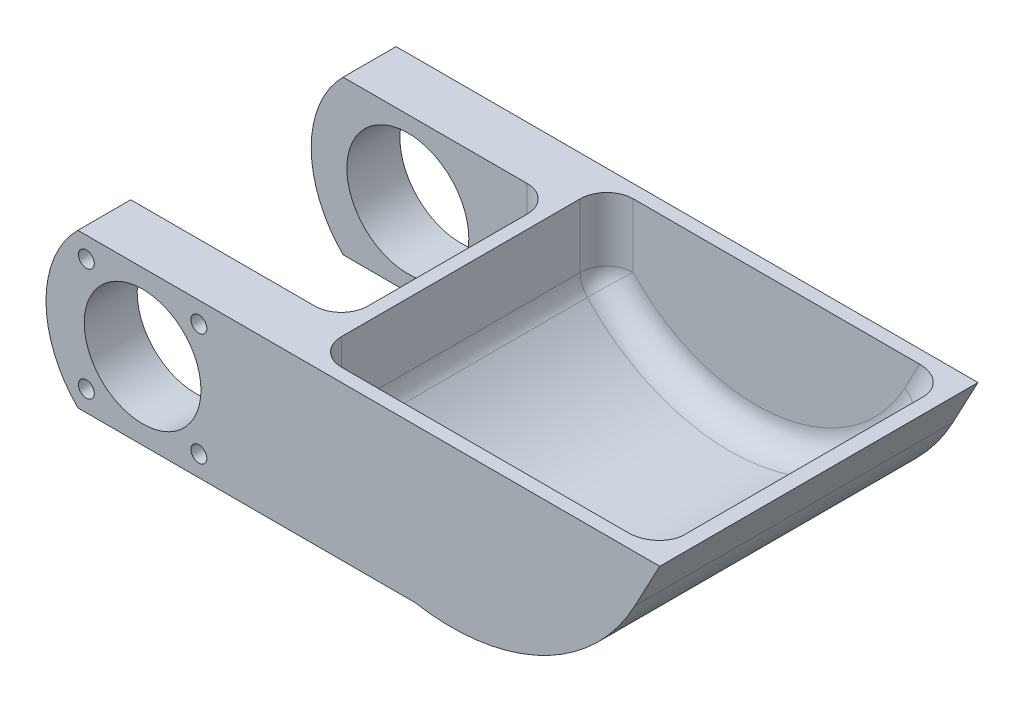
SolidWorks part; units mm, degrees
material "7075-T6, Plate (SS)"
ref_plane "Front Plane" through (0, 0, 0) normal (0, 0, 1) x (1, 0, 0)
ref_plane "Top Plane" through (0, 0, 0) normal (0, 1, 0) x (1, 0, 0)
ref_plane "Right Plane" through (0, 0, 0) normal (1, 0, 0) x (0, 0, -1)
sketch "Sketch1" plane through (0, 0, 0) normal (0, 1, 0) x (1, 0, 0)
  line L1 (0, 0) -> (-88.9, 0)
  line L2 (0, 0) -> (0, 76.2)
  line L3 (0, 76.2) -> (-88.9, 76.2)
  line L4 (-88.9, 0) -> (-88.9, 76.2)
  dimension "D1" = 88.9
  dimension "D2" = 76.2
extrude "Boss-Extrude1" add sketch "Sketch1" against normal blind 37.592
sketch "Sketch2" plane through (0, 0, 0) normal (0, 0, 1) x (1, 0, 0)
  line L0 (-88.9, 0) -> (-88.9, -18.796)
  line L2 (-88.9, -37.592) -> (-88.9, 0) construction
  line L8 (0, 0) -> (-5.9722, -11.2082)
  line L9 (0, 0) -> (-88.9, 0)
  line L10 (-88.9, -37.592) -> (0, -37.592) construction
  arc A0 (-88.9, -18.796) -> (-5.9722, -11.2082) centre (-49.9262, 12.2124) ccw
  dimension "D1" = 12.7
extrude "Cut-Extrude1" cut sketch "Sketch2" against normal up to next
shell "Shell1" thickness 3.175 removed face at (-44.45, 0, -38.1)
sketch "Sketch15" plane through (-88.9, 0, 0) normal (-1, 0, 0) x (0, 0, 1)
sketch "Sketch16" plane through (-88.9, 0, 0) normal (-1, 0, 0) x (0, 0, 1)
  line L0 (0, 0) -> (0, -36.83)
  line L1 (0, -36.83) -> (-12.6646, -36.83)
  line L2 (-12.6646, -36.83) -> (-12.6646, 0)
  line L3 (-76.2, 0) -> (0, 0) construction
  line L4 (-12.6646, 0) -> (0, 0)
  line L5 (-76.2, 0) -> (-76.2, -36.83)
  line L6 (-76.2, -36.83) -> (-63.5071, -36.83)
  line L7 (-63.5071, -36.83) -> (-63.5071, 0)
  line L8 (-63.5071, 0) -> (-76.2, 0)
  dimension "D1" = 36.83
  dimension "D2" = 36.83
extrude "Boss-Extrude4" add sketch "Sketch16" along normal blind 63.5 and the other way up to next
sketch "Sketch18" plane through (0, 0, -63.5071) normal (0, 0, 1) x (1, 0, 0)
  line L0 (-88.9, -18.796) -> (-88.9, 0) construction
  circle A0 centre (-123.825, -18.415) radius 14.605
  dimension "D1" = 34.925
  dimension "D2" = 29.21
extrude "Cut-Extrude2" cut sketch "Sketch18" against normal up to next
sketch "Sketch20" plane through (0, 0, -12.6646) normal (0, 0, -1) x (-1, 0, 0)
  line L2 (88.9, 0) -> (88.9, -18.796) construction
  circle A0 centre (123.825, -18.415) radius 13.97
  circle A1 centre (137.2954, -4.9446) radius 1.905
  circle A2 centre (137.2954, -31.8854) radius 1.905
  circle A3 centre (110.3546, -31.8854) radius 1.905
  circle A4 centre (110.3546, -4.9446) radius 1.905
  dimension "D1" = 34.925
  dimension "D6" = 27.94
  dimension "D7" = 3.81
  dimension "D8" = 3.81
  dimension "D9" = 3.81
  dimension "D10" = 3.81
  dimension "D4" = 26.9408
  dimension "D5" = 26.9408
extrude "Cut-Extrude3" cut sketch "Sketch20" against normal up to next
sketch "Sketch21" plane through (0, 0, -12.6646) normal (0, 0, -1) x (-1, 0, 0)
sketch "Sketch22" plane through (0, 0, -76.2) normal (0, 0, -1) x (-1, 0, 0)
  line L0 (0, 0) -> (152.4, 0) construction
  line L1 (58.605, -36.83) -> (152.4, -36.83) construction
  line L2 (139.3293, 0) -> (152.4, 0)
  line L3 (152.4, 0) -> (152.4, -36.83)
  line L4 (152.4, -36.83) -> (139.3293, -36.83)
  arc A0 (139.3293, 0) -> (139.3293, -36.83) centre (120.9143, -18.415) cw
extrude "Cut-Extrude4" cut sketch "Sketch22" against normal through all
fillet "Fillet2" radius 6.35 11 edges at (-6.1859, -4.8576, -73.025) (-6.1859, -4.8576, -3.175) (-85.725, -8.8332, -73.025) (-45.1335, -34.17, -73.025) (-85.725, -17.6665, -38.1) (-85.725, -8.8332, -3.175) (-45.1335, -34.17, -3.175)
